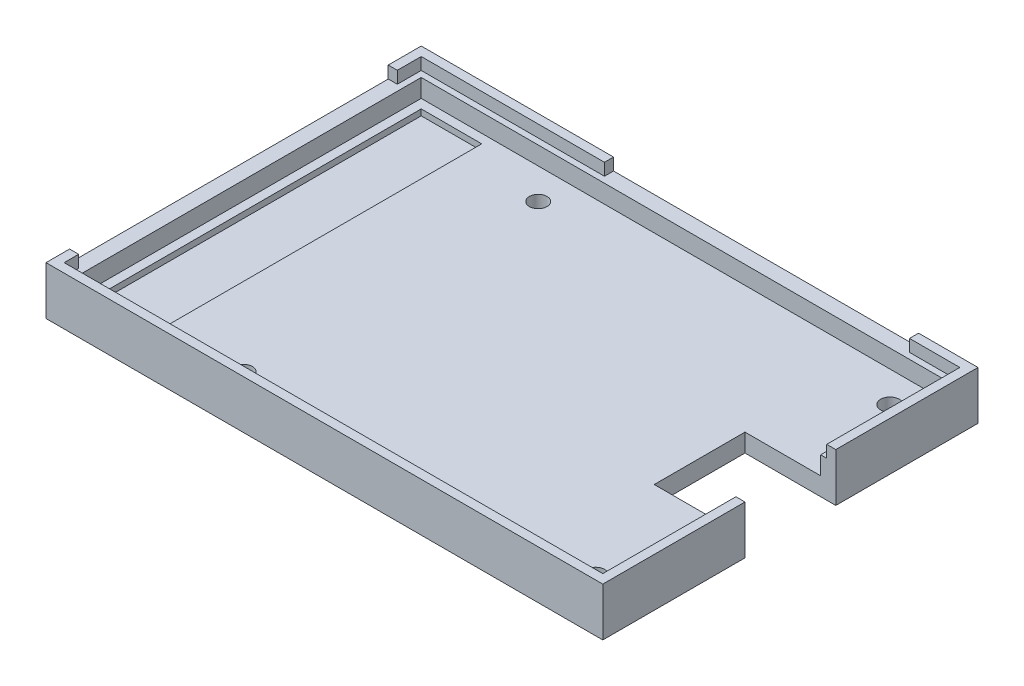
SolidWorks part; units mm, degrees
material "ABS"
ref_plane "Front" through (0, 0, 0) normal (0, 0, 1) x (1, 0, 0)
ref_plane "Top" through (0, 0, 0) normal (0, 1, 0) x (1, 0, 0)
ref_plane "Right" through (0, 0, 0) normal (1, 0, 0) x (0, 0, -1)
sketch "Croquis2" plane through (0, 0, 0) normal (0, 1, 0) x (1, 0, 0)
  line L1 (-46, -31) -> (46, -31)
  line L2 (-46, -31) -> (-46, 31)
  line L3 (-46, 31) -> (46, 31)
  line L4 (46, -31) -> (46, 31)
  line L5 (-46, -31) -> (46, 31) construction
  line L6 (-46, 31) -> (46, -31) construction
  point P0 (0, 0)
  dimension "D1" = 92
  dimension "D2" = 62
extrude "Saliente-Extruir1" add sketch "Croquis2" along normal blind 8
sketch "Croquis3" plane through (0, 8, 0) normal (0, 1, 0) x (1, 0, 0)
  line L0 (46, 31) -> (-46, 31) construction
  line L1 (44.5, -29.5) -> (-44.5, -29.5)
  line L2 (44.5, -29.5) -> (44.5, 29.5)
  line L3 (44.5, 29.5) -> (-44.5, 29.5)
  line L4 (-44.5, -29.5) -> (-44.5, 29.5)
  line L5 (44.5, -29.5) -> (-44.5, 29.5) construction
  line L6 (44.5, 29.5) -> (-44.5, -29.5) construction
  line L7 (-46, 31) -> (-46, -31) construction
  point P0 (0, 0)
  dimension "D1" = 1.5
  dimension "D2" = 1.5
extrude "Cortar-Extruir1" cut sketch "Croquis3" against normal blind 2
sketch "Croquis4" plane through (0, 6, 0) normal (0, 1, 0) x (1, 0, 0)
  line L0 (44.5, 29.5) -> (-44.5, 29.5) construction
  line L1 (-43.5, -28.5) -> (43.5, -28.5)
  line L2 (-43.5, -28.5) -> (-43.5, 28.5)
  line L3 (-43.5, 28.5) -> (43.5, 28.5)
  line L4 (43.5, -28.5) -> (43.5, 28.5)
  line L5 (-43.5, -28.5) -> (43.5, 28.5) construction
  line L6 (-43.5, 28.5) -> (43.5, -28.5) construction
  line L7 (44.5, -29.5) -> (44.5, 29.5) construction
  point P0 (0, 0)
  dimension "D1" = 1
  dimension "D2" = 1
extrude "Cortar-Extruir2" cut sketch "Croquis4" against normal blind 3
sketch "Croquis5" plane through (0, 3, 0) normal (0, 1, 0) x (1, 0, 0)
  line L0 (43.5, 28.5) -> (-43.5, 28.5) construction
  line L1 (-32, -26.6325) -> (-42, -26.6325)
  line L2 (-32, -26.6325) -> (-32, 27)
  line L3 (-32, 27) -> (-42, 27)
  line L4 (-42, -26.6325) -> (-42, 27)
  line L5 (-32, -26.6325) -> (-42, 27) construction
  line L6 (-32, 27) -> (-42, -26.6325) construction
  line L7 (-43.5, 28.5) -> (-43.5, -28.5) construction
  point P0 (-37, 0.1837)
  dimension "D1" = 10
  dimension "D2" = 1.5
  dimension "D3" = 1.5
extrude "Cortar-Extruir3" cut sketch "Croquis5" against normal blind 1
ref_plane "Plano1" through (0, 5, 0) normal (0, 1, 0) x (1, 0, 0)
sketch "Croquis6" plane through (0, 5, 0) normal (0, 1, 0) x (1, 0, 0)
  line L0 (46, -31) -> (46, 31) construction
  line L1 (31, 5) -> (46, 5)
  line L2 (31, 5) -> (31, -5)
  line L3 (31, -5) -> (46, -5)
  line L4 (46, 5) -> (46, -5)
  line L5 (31, 5) -> (46, -5) construction
  line L6 (31, -5) -> (46, 5) construction
  line L7 (-999.6662, 0) -> (49000.3338, 0) construction
  point P0 (38.5, 0)
  point P8 (31, 0)
  dimension "D1" = 15
  dimension "D2" = 10
extrude "Cortar-Extruir4" cut sketch "Croquis6" against normal up to surface (3 mm away) up to face at (-37, 2, -0.1837)
sketch "Croquis7" plane through (0, 2, 0) normal (0, 1, 0) x (1, 0, 0)
  line L0 (46, 5) -> (46, -5) construction
  circle A0 centre (46, 0) radius 5
extrude "Cortar-Extruir5" cut sketch "Croquis7" against normal through all
fillet "Redondeo1" radius 5 1 edges at (41, 2, 0)
sketch "Croquis8" plane through (0, 3, 0) normal (0, 1, 0) x (1, 0, 0)
  line L0 (39, 24) -> (39, -24) construction
  line L1 (46, -31) -> (46, 31) construction
  line L2 (39, 24) -> (-19, 24) construction
  line L3 (-19, 24) -> (-19, -24) construction
  line L4 (-19, -24) -> (39, -24) construction
  line L5 (46, 31) -> (-46, 31) construction
  line L6 (-46, -31) -> (46, -31) construction
  circle A0 centre (39, -24) radius 1.5
  circle A1 centre (39, 24) radius 1.5
  circle A2 centre (-19, 24) radius 1.5
  circle A3 centre (-19, -24) radius 1.5
  dimension "D2" = 3
  dimension "D3" = 3
  dimension "D5" = 3
  dimension "D6" = 3
  dimension "D1" = 7
  dimension "D4" = 58
  dimension "D7" = 7
  dimension "D8" = 7
sketch "Croquis9" plane through (0, 8, 0) normal (0, 1, 0) x (1, 0, 0)
  line L0 (-43.5, 28.5) -> (-43.5, -28.5) construction
  line L1 (-43.5, -27.1057) -> (-46, -27.1057)
  line L2 (-43.5, -27.1057) -> (-43.5, -10.0965)
  line L3 (-43.5, -10.0965) -> (-46, -10.0965)
  line L4 (-46, -27.1057) -> (-46, -10.0965)
  line L5 (-46, 31) -> (-46, -31) construction
  line L6 (-43.5, 28.5) -> (-43.5, -28.5) construction
  line L7 (-43.5, -6.5224) -> (-46, -6.5224)
  line L8 (-43.5, -6.5224) -> (-43.5, 7.4776)
  line L9 (-43.5, 7.4776) -> (-46, 7.4776)
  line L10 (-46, -6.5224) -> (-46, 7.4776)
  line L11 (-46.2146, -26.6057) -> (-25.3253, -26.6057) construction
  line L12 (-43.5, 11.4015) -> (-46, 11.4015)
  line L13 (-43.5, 11.4015) -> (-43.5, 25.5516)
  line L14 (-43.5, 25.5516) -> (-46, 25.5516)
  line L15 (-46, 11.4015) -> (-46, 25.5516)
  line L16 (-25.3253, -10.5965) -> (-46.2146, -10.5965) construction
  line L17 (-47.1776, -6.0224) -> (-29.5382, -6.0224) construction
  line L18 (-29.5382, 6.9776) -> (-47.1776, 6.9776) construction
  line L19 (-47.1776, 11.9015) -> (-29.5382, 11.9015) construction
  line L20 (-29.5382, 25.0516) -> (-47.1776, 25.0516) construction
  line L21 (46, 31) -> (-46, 31) construction
  line L22 (36.1586, 31) -> (26.1932, 31)
  line L23 (36.1586, 31) -> (36.1586, 28.5)
  line L24 (36.1586, 28.5) -> (26.1932, 28.5)
  line L25 (26.1932, 31) -> (26.1932, 28.5)
  line L26 (43.5, 28.5) -> (-43.5, 28.5) construction
  line L27 (43.5, 28.5) -> (-43.5, 28.5) construction
  line L28 (19.8422, 31) -> (12.5477, 31)
  line L29 (19.8422, 31) -> (19.8422, 28.5)
  line L30 (19.8422, 28.5) -> (12.5477, 28.5)
  line L31 (12.5477, 31) -> (12.5477, 28.5)
  line L32 (6.2881, 31) -> (-1.1323, 31)
  line L33 (6.2881, 31) -> (6.2881, 28.5)
  line L34 (6.2881, 28.5) -> (-1.1323, 28.5)
  line L35 (-1.1323, 31) -> (-1.1323, 28.5)
  line L36 (35.6586, 28.9255) -> (35.6586, 21.2292) construction
  line L37 (-9.2258, 31) -> (-14.2258, 31)
  line L38 (-9.2258, 31) -> (-9.2258, 28.5)
  line L39 (-9.2258, 28.5) -> (-14.2258, 28.5)
  line L40 (-14.2258, 31) -> (-14.2258, 28.5)
  line L41 (26.6932, 21.2292) -> (26.6932, 28.9255) construction
  line L42 (19.3422, 20.626) -> (19.3422, 28.6409) construction
  line L43 (13.0477, 28.6409) -> (13.0477, 23.8845) construction
  line L44 (-0.6323, 28.6409) -> (-0.6323, 20.626) construction
  line L45 (5.7881, 20.626) -> (5.7881, 28.6409) construction
  line L46 (-11.7258, 31) -> (-11.7258, 27.247) construction
  line L51 (-8.1379, 27.247) -> (-15.3137, 27.247) construction
  line L52 (-8.1379, 27.247) -> (-15.3137, 27.247) construction
  dimension "D1" = 0.5
  dimension "D2" = 0.5
  dimension "D3" = 0.5
  dimension "D4" = 0.5
  dimension "D5" = 0.5
  dimension "D6" = 0.5
  dimension "D7" = 0.5
  dimension "D8" = 0.5
  dimension "D9" = 0.5
  dimension "D10" = 0.5
  dimension "D11" = 0.5
  dimension "D12" = 0.5
  dimension "D13" = 5
extrude "Cortar-Extruir7" cut sketch "Croquis9" against normal blind 2
sketch "Croquis10" plane through (0, 3, 0) normal (0, 1, 0) x (1, 0, 0)
  circle A0 centre (39.0422, -25.2384) radius 1.4924
  circle A1 centre (39.0422, -25.2384) radius 1.4924 construction
  circle A2 centre (39.0422, 23.4108) radius 1.5411
  circle A3 centre (-19.0815, 23.4108) radius 1.4546
  circle A4 centre (-19.0815, -25.2384) radius 1.4361
extrude "Cortar-Extruir8" cut sketch "Croquis10" against normal through all
sketch "Croquis11" plane through (46, 0, 0) normal (1, 0, 0) x (0, 0, -1)
  line L0 (-31, 8) -> (31, 8) construction
  line L1 (-7.5, 8) -> (7.5, 8)
  line L2 (-7.5, 8) -> (-7.5, 0)
  line L3 (-7.5, 0) -> (7.5, 0)
  line L4 (7.5, 8) -> (7.5, 0)
  line L5 (5, 0) -> (31, 0) construction
  line L6 (0, 2.652) -> (0, 13.348) construction
  line L7 (-5, 3) -> (5, 3) construction
  point P10 (0, 8)
  point P13 (0, 3)
  dimension "D1" = 15
extrude "Cortar-Extruir9" cut sketch "Croquis11" against normal up to surface (15 mm away) up to face at (31, 2.5, 0)
sketch "Croquis12" plane through (0, 0, -31) normal (0, 0, -1) x (-1, 0, 0)
  line L0 (-46, 8) -> (-36.1586, 8) construction
  line L1 (-36.1817, 8) -> (14.2258, 8)
  line L2 (-36.1817, 8) -> (-36.1817, 6)
  line L3 (-36.1817, 6) -> (14.2258, 6)
  line L4 (14.2258, 8) -> (14.2258, 6)
extrude "Cortar-Extruir10" cut sketch "Croquis12" against normal up to surface (2.5 mm away) up to face at (0, 4.5, -28.5)
sketch "Croquis13" plane through (-46, 0, 0) normal (-1, 0, 0) x (0, 0, 1)
  line L0 (-25.5516, 6) -> (-25.5516, 8) construction
  line L1 (-25.5516, 8) -> (27.1057, 8)
  line L2 (-25.5516, 8) -> (-25.5516, 6)
  line L3 (-25.5516, 6) -> (27.1057, 6)
  line L4 (27.1057, 8) -> (27.1057, 6)
  line L5 (-31, 8) -> (-25.5516, 8) construction
extrude "Cortar-Extruir11" cut sketch "Croquis13" against normal up to surface (2.5 mm away) up to face at (-43.5, 4.5, 0)
